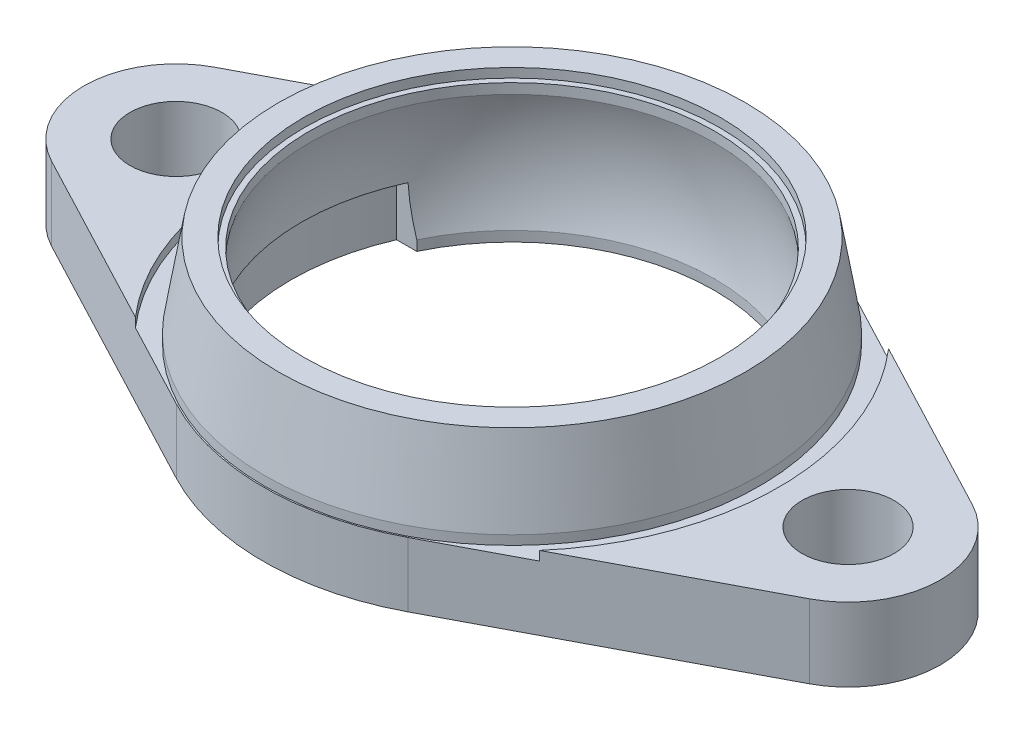
SolidWorks part; units mm, degrees
material "Zinc AC41A Alloy, As Cast"
ref_plane "Front Plane" through (0, 0, 0) normal (0, 0, 1) x (1, 0, 0)
ref_plane "Top Plane" through (0, 0, 0) normal (0, 1, 0) x (1, 0, 0)
ref_plane "Right Plane" through (0, 0, 0) normal (1, 0, 0) x (0, 0, -1)
ref_axis "Bearing Axis" through (0, -0.425, 0) along (0, 1, 0)
sketch "Sketch1" plane through (0, 0, 0) normal (0, 1, 0) x (1, 0, 0)
  line L0 (-18.25, 0) -> (0, 0) construction
  line L1 (0, 0) -> (18.25, 0) construction
  line L2 (20.5788, 4.4246) -> (6.2877, 11.9463)
  line L3 (-20.5788, 4.4246) -> (-6.2877, 11.9463)
  line L4 (-20.5788, -4.4246) -> (-6.2877, -11.9463)
  line L5 (6.2877, -11.9463) -> (20.5788, -4.4246)
  circle A0 centre (-18.25, 0) radius 2.5 construction
  circle A1 centre (18.25, 0) radius 2.5 construction
  circle A2 centre (0, 0) radius 11
  arc A3 (6.2877, 11.9463) -> (-6.2877, 11.9463) centre (0, 0) ccw
  arc A4 (-20.5788, 4.4246) -> (-20.5788, -4.4246) centre (-18.25, 0) ccw
  arc A5 (20.5788, -4.4246) -> (20.5788, 4.4246) centre (18.25, 0) ccw
  arc A6 (-6.2877, -11.9463) -> (6.2877, -11.9463) centre (0, 0) ccw
  dimension "D1" = 27
  dimension "D2" = 22
  dimension "D3" = 10
  dimension "D4" = 5
  dimension "D5" = 36.5
extrude "Flange" add sketch "Sketch1" along normal blind 4
sketch "Sketch2" plane through (0, 0, 0) normal (0, 0, 1) x (1, 0, 0)
  line L0 (-13.425, 4) -> (-12.675, 8.5)
  line L1 (-12.675, 8.5) -> (-11.3, 8.5)
  line L2 (-11.3, 8.5) -> (-11.3, 8)
  line L3 (-11.3, 8) -> (-11, 8)
  line L4 (-11, 8) -> (-11, 4)
  line L5 (-11, 4) -> (-13.425, 4)
  line L6 (0, 0) -> (0, 4) construction
  line L7 (0, 4) -> (-11, 4) construction
  line L8 (11, 4) -> (-11, 4) construction
  dimension "D1" = 4.5
  dimension "D2" = 22
  dimension "D3" = 26.85
  dimension "D4" = 25.35
  dimension "D5" = 0.5
  dimension "D6" = 0.3
revolve "Bearing Seat" add sketch "Sketch2" angle 360 about L6
sketch "Sketch3" plane through (0, 4, 0) normal (0, 1, 0) x (1, 0, 0)
  line L4 (20.5788, 4.4246) -> (6.2877, 11.9463)
  line L5 (-6.2877, 11.9463) -> (-20.5788, 4.4246)
  line L6 (-20.5788, -4.4246) -> (-6.2877, -11.9463)
  line L7 (6.2877, -11.9463) -> (20.5788, -4.4246)
  line L8 (10.9702, 9.4818) -> (6.2877, 11.9463)
  line L9 (-6.2877, 11.9463) -> (-10.9702, 9.4818)
  line L10 (-10.9702, -9.4818) -> (-6.2877, -11.9463)
  line L11 (6.2877, -11.9463) -> (10.9702, -9.4818)
  arc A0 (-10.9702, 9.4818) -> (-10.9702, -9.4818) centre (0, 0) ccw
  circle A2 centre (0, 0) radius 13.425 construction
  arc A3 (10.9702, -9.4818) -> (10.9702, 9.4818) centre (0, 0) ccw
  arc A4 (20.5788, -4.4246) -> (20.5788, 4.4246) centre (18.25, 0) ccw
  arc A5 (6.2877, 11.9463) -> (-6.2877, 11.9463) centre (0, 0) ccw
  arc A6 (-20.5788, 4.4246) -> (-20.5788, -4.4246) centre (-18.25, 0) ccw
  arc A7 (-6.2877, -11.9463) -> (6.2877, -11.9463) centre (0, 0) ccw
  circle A8 centre (0, 0) radius 13.425
  arc A9 (-6.2877, -11.9463) -> (6.2877, -11.9463) centre (0, 0) ccw construction
  arc A10 (-6.2877, -11.9463) -> (6.2877, -11.9463) centre (0, 0) ccw
  arc A11 (6.2877, 11.9463) -> (-6.2877, 11.9463) centre (0, 0) ccw construction
  arc A12 (6.2877, 11.9463) -> (-6.2877, 11.9463) centre (0, 0) ccw
  dimension "D2" = 29
  dimension "D1" = 0
extrude "Top Recess" cut sketch "Sketch3" against normal blind 0.5
sketch "Sketch5" plane through (0, 0, 0) normal (0, -1, 0) x (1, 0, 0)
  line L0 (17.0094, 4.3256) -> (5.4726, 10.3977)
  line L1 (-5.4726, 10.3977) -> (-17.0094, 4.3256)
  line L2 (-17.0094, -4.3256) -> (-5.4726, -10.3977)
  line L3 (5.4726, -10.3977) -> (17.0094, -4.3256)
  line L4 (20.5788, 4.4246) -> (6.2877, 11.9463)
  line L5 (-6.2877, 11.9463) -> (-20.5788, 4.4246)
  line L6 (-20.5788, -4.4246) -> (-6.2877, -11.9463)
  line L7 (6.2877, -11.9463) -> (20.5788, -4.4246)
  line L8 (20.5788, 4.4246) -> (6.2877, 11.9463) construction
  line L9 (-6.2877, 11.9463) -> (-20.5788, 4.4246) construction
  line L10 (-20.5788, -4.4246) -> (-6.2877, -11.9463) construction
  line L11 (6.2877, -11.9463) -> (20.5788, -4.4246) construction
  line L13 (-5.4726, 10.3977) -> (-19.7637, 2.876) construction
  line L14 (-19.7637, -2.876) -> (-5.4726, -10.3977) construction
  line L15 (5.4726, -10.3977) -> (19.7637, -2.876) construction
  line L16 (19.7637, 2.876) -> (5.4726, 10.3977) construction
  arc A0 (5.4726, 10.3977) -> (-5.4726, 10.3977) centre (0, 0) ccw
  arc A2 (-5.4726, -10.3977) -> (5.4726, -10.3977) centre (0, 0) ccw
  arc A4 (20.5788, -4.4246) -> (20.5788, 4.4246) centre (18.25, 0) ccw
  arc A5 (6.2877, 11.9463) -> (-6.2877, 11.9463) centre (0, 0) ccw
  arc A6 (-20.5788, 4.4246) -> (-20.5788, -4.4246) centre (-18.25, 0) ccw
  arc A7 (-6.2877, -11.9463) -> (6.2877, -11.9463) centre (0, 0) ccw
  arc A8 (20.5788, -4.4246) -> (20.5788, 4.4246) centre (18.25, 0) ccw construction
  arc A9 (6.2877, 11.9463) -> (-6.2877, 11.9463) centre (0, 0) ccw construction
  arc A10 (-20.5788, 4.4246) -> (-20.5788, -4.4246) centre (-18.25, 0) ccw construction
  arc A11 (-6.2877, -11.9463) -> (6.2877, -11.9463) centre (0, 0) ccw construction
  arc A12 (-17.0094, -4.3256) -> (-17.0094, 4.3256) centre (-18.25, 0) ccw
  arc A13 (17.0094, 4.3256) -> (17.0094, -4.3256) centre (18.25, 0) ccw
  arc A14 (-19.7637, 2.876) -> (-19.7637, -2.876) centre (-18.25, 0) ccw construction
  arc A15 (19.7637, -2.876) -> (19.7637, 2.876) centre (18.25, 0) ccw construction
  dimension "D3" = 9
  dimension "D1" = 0
  dimension "D2" = 1.75
extrude "Bottom Recess 1" cut sketch "Sketch5" against normal blind 0.5
sketch "Sketch6" plane through (0, 0.5, 0) normal (0, -1, 0) x (1, 0, 0)
  line L0 (-11.0199, 4.75) -> (11.0199, 4.75)
  line L1 (-11.0199, -4.75) -> (11.0199, -4.75)
  circle A0 centre (0, 0) radius 11 construction
  circle A1 centre (0, 0) radius 11 construction
  arc A2 (11.0199, -4.75) -> (11.0199, 4.75) centre (0, 0) ccw
  arc A3 (-11.0199, 4.75) -> (-11.0199, -4.75) centre (0, 0) ccw
  circle A4 centre (0, 0) radius 12 construction
  point P9 (12, 0)
  dimension "D2" = 9.5
  dimension "D1" = 1
extrude "Bottom Recess 2" cut sketch "Sketch6" against normal blind 3
hole_wizard "Mounting Hole (M5x0.8)" positions "Sketch10" profile "Sketch9" tap size "M6x1.0" standard "ANSI Metric" end condition through all
sketch "Sketch10" plane through (0, 4, 0) normal (0, 1, 0) x (1, 0, 0)
  point P0 (18.25, 0)
  point P3 (-18.25, 0)
sketch "Sketch9" plane through (18.25, 4, 0) normal (1, 0, 0) x (0, 0, 1)
  line L0 (0, 0) -> (0, 4)
  line L1 (0, 4) -> (2.5, 4)
  line L2 (2.5, 4) -> (2.5, 0)
  line L5 (2.5, 0) -> (0, 0)
  line L11 (0, -6.35) -> (0, 107.95) construction
  dimension "Thru Tap Drill Dia." = 5
  dimension "Thru Tap Drill Depth" = 4
cosmetic thread "Hole Thread3" parameters "D2"=6
cosmetic thread "Hole Thread4" parameters "D2"=6
sketch "Sketch11" plane through (0, 0, 0) normal (0, 0, 1) x (1, 0, 0)
  line L0 (0, 8.5) -> (0, 4.25) construction
  line L1 (11.3, 8.5) -> (-11.3, 8.5) construction
  line L2 (0, 4.25) -> (0, 0) construction
  line L3 (0, 15.706) -> (0, -7.206)
  arc A0 (0, -7.206) -> (0, 15.706) centre (0, 4.25) ccw
  dimension "D1" = 22.912
revolve "Cut-Revolve1" cut sketch "Sketch11" angle 360 about L0
